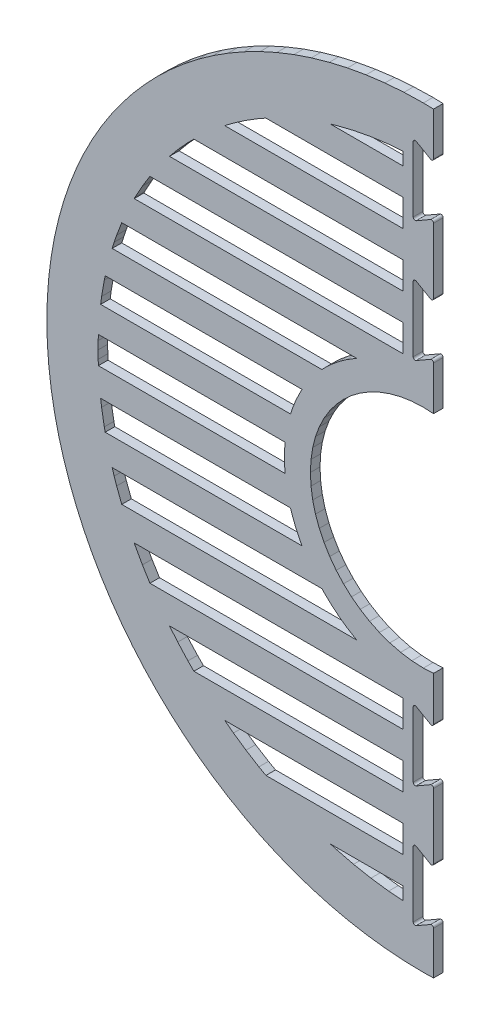
SolidWorks part; units mm, degrees
ref_plane "Front Plane" through (0, 0, 0) normal (0, 0, 1) x (1, 0, 0)
ref_plane "Top Plane" through (0, 0, 0) normal (0, 1, 0) x (1, 0, 0)
ref_plane "Right Plane" through (0, 0, 0) normal (1, 0, 0) x (0, 0, -1)
sketch "Model" plane through (0, 0, 0) normal (0, 0, 1) x (1, 0, 0)
  line L0 (-29.1025, -97.3667) -> (-27.1353, -97.9361)
  line L1 (-27.1353, -97.9361) -> (-21.8097, -99.2536)
  line L2 (-21.8097, -99.2536) -> (-16.3779, -100.2869)
  line L3 (-16.3779, -100.2869) -> (-10.848, -101.0278)
  line L4 (-10.848, -101.0278) -> (-5.2283, -101.4679)
  line L5 (-5.2283, -101.4679) -> (-4, -101.5146)
  line L6 (-4, -101.5146) -> (-4, -97.3667)
  line L7 (-4, -97.3667) -> (-29.1025, -97.3667)
  line L8 (4, -91.5563) -> (4, -100.5663)
  line L9 (4, -100.5663) -> (6.4923, -101.4734)
  line L10 (6.4923, -101.4734) -> (8.9399, -101.2903)
  line L11 (8.9399, -101.2903) -> (16.2223, -100.3929)
  line L12 (16.2223, -100.3929) -> (23.3353, -98.9929)
  line L13 (23.3353, -98.9929) -> (23.9888, -98.8316)
  line L14 (23.9888, -98.8316) -> (4, -91.5563)
  line L15 (-62.0452, -80.4333) -> (-59.3119, -82.4998)
  line L16 (-59.3119, -82.4998) -> (-55.4039, -85.1786)
  line L17 (-55.4039, -85.1786) -> (-51.3677, -87.677)
  line L18 (-51.3677, -87.677) -> (-49.1681, -88.9)
  line L19 (-49.1681, -88.9) -> (-4, -88.9)
  line L20 (-4, -88.9) -> (-4, -80.4333)
  line L21 (-4, -80.4333) -> (-62.0452, -80.4333)
  line L22 (4, -73.5362) -> (4, -82.5462)
  line L23 (4, -82.5462) -> (37.2469, -94.6471)
  line L24 (37.2469, -94.6471) -> (41.3341, -92.9428)
  line L25 (41.3341, -92.9428) -> (45.5839, -90.9334)
  line L26 (45.5839, -90.9334) -> (48.1117, -89.5915)
  line L27 (48.1117, -89.5915) -> (4, -73.5362)
  line L28 (-79.2988, -63.5) -> (-76.7248, -66.6048)
  line L29 (-76.7248, -66.6048) -> (-73.5451, -70.098)
  line L30 (-73.5451, -70.098) -> (-71.6792, -71.9667)
  line L31 (-71.6792, -71.9667) -> (-4, -71.9667)
  line L32 (-4, -71.9667) -> (-4, -63.5)
  line L33 (-4, -63.5) -> (-79.2988, -63.5)
  line L34 (4, -55.5161) -> (4, -64.5262)
  line L35 (4, -64.5262) -> (57.3994, -83.962)
  line L36 (57.3994, -83.962) -> (57.6454, -83.8007)
  line L37 (57.6454, -83.8007) -> (61.4183, -81.0733)
  line L38 (61.4183, -81.0733) -> (65.0584, -78.18)
  line L39 (65.0584, -78.18) -> (65.4148, -77.8693)
  line L40 (65.4148, -77.8693) -> (4, -55.5161)
  line L41 (-90.3108, -46.5667) -> (-90.0607, -47.0729)
  line L42 (-90.0607, -47.0729) -> (-87.7545, -51.2354)
  line L43 (-87.7545, -51.2354) -> (-85.4115, -55.0333)
  line L44 (-85.4115, -55.0333) -> (-4, -55.0333)
  line L45 (-4, -55.0333) -> (-4, -46.5667)
  line L46 (-4, -46.5667) -> (-90.3108, -46.5667)
  line L47 (13.9184, -41.106) -> (13.6646, -41.1963)
  line L48 (13.6646, -41.1963) -> (9.1415, -42.427)
  line L49 (9.1415, -42.427) -> (4.4365, -43.1676)
  line L50 (4.4365, -43.1676) -> (4, -43.2008)
  line L51 (4, -43.2008) -> (4, -46.5061)
  line L52 (4, -46.5061) -> (72.4083, -71.4047)
  line L53 (72.4083, -71.4047) -> (75.1264, -68.5601)
  line L54 (75.1264, -68.5601) -> (78.18, -65.0584)
  line L55 (78.18, -65.0584) -> (78.5271, -64.6217)
  line L56 (78.5271, -64.6217) -> (13.9184, -41.106)
  line L57 (-97.2071, -29.6333) -> (-96.5817, -31.625)
  line L58 (-96.5817, -31.625) -> (-95.8036, -33.9098)
  line L59 (-95.8036, -33.9098) -> (-94.207, -38.1)
  line L60 (-94.207, -38.1) -> (-20.7604, -38.1)
  line L61 (-20.7604, -38.1) -> (-21.4848, -37.7079)
  line L62 (-21.4848, -37.7079) -> (-23.9895, -36.1628)
  line L63 (-23.9895, -36.1628) -> (-26.3777, -34.4565)
  line L64 (-26.3777, -34.4565) -> (-28.6418, -32.5965)
  line L65 (-28.6418, -32.5965) -> (-30.7744, -30.5904)
  line L66 (-30.7744, -30.5904) -> (-31.6842, -29.6333)
  line L67 (-31.6842, -29.6333) -> (-97.2071, -29.6333)
  line L68 (31.7453, -29.5744) -> (30.6825, -30.6825)
  line L69 (30.6825, -30.6825) -> (28.0009, -33.1492)
  line L70 (28.0009, -33.1492) -> (25.1189, -35.3861)
  line L71 (25.1189, -35.3861) -> (24.3655, -35.8984)
  line L72 (24.3655, -35.8984) -> (83.8612, -57.5531)
  line L73 (83.8612, -57.5531) -> (86.3569, -53.745)
  line L74 (86.3569, -53.745) -> (88.4468, -50.2121)
  line L75 (88.4468, -50.2121) -> (31.7453, -29.5744)
  line L76 (40.7776, -14.8418) -> (40.5732, -15.4165)
  line L77 (40.5732, -15.4165) -> (39.1128, -18.8121)
  line L78 (39.1128, -18.8121) -> (37.3789, -22.0511)
  line L79 (37.3789, -22.0511) -> (37.0937, -22.511)
  line L80 (37.0937, -22.511) -> (92.3359, -42.6176)
  line L81 (92.3359, -42.6176) -> (92.9428, -41.3341)
  line L82 (92.9428, -41.3341) -> (94.7589, -36.9789)
  line L83 (94.7589, -36.9789) -> (95.5572, -34.78)
  line L84 (95.5572, -34.78) -> (40.7776, -14.8418)
  line L85 (-100.8122, -12.7) -> (-100.5006, -14.9994)
  line L86 (-100.5006, -14.9994) -> (-99.6609, -19.8552)
  line L87 (-99.6609, -19.8552) -> (-99.3846, -21.1667)
  line L88 (-99.3846, -21.1667) -> (-37.8853, -21.1667)
  line L89 (-37.8853, -21.1667) -> (-38.7638, -19.5198)
  line L90 (-38.7638, -19.5198) -> (-40.0074, -16.8291)
  line L91 (-40.0074, -16.8291) -> (-41.069, -14.0429)
  line L92 (-41.069, -14.0429) -> (-41.4935, -12.7)
  line L93 (-41.4935, -12.7) -> (-100.8122, -12.7)
  line L94 (85.2546, -4) -> (101.2046, -9.8053)
  line L95 (101.2046, -9.8053) -> (101.2903, -8.9399)
  line L96 (101.2903, -8.9399) -> (101.6001, -4)
  line L97 (101.6001, -4) -> (85.2546, -4)
  line L98 (43.2008, -4) -> (43.1676, -4.4365)
  line L99 (43.1676, -4.4365) -> (42.932, -6.3385)
  line L100 (42.932, -6.3385) -> (42.8879, -6.5999)
  line L101 (42.8879, -6.5999) -> (98.134, -26.7078)
  line L102 (98.134, -26.7078) -> (98.4177, -25.6655)
  line L103 (98.4177, -25.6655) -> (99.9812, -18.6131)
  line L104 (99.9812, -18.6131) -> (100.0206, -18.3844)
  line L105 (100.0206, -18.3844) -> (60.4997, -4)
  line L106 (60.4997, -4) -> (43.2008, -4)
  line L107 (-101.5066, 4.2333) -> (-101.5689, 2.5406)
  line L108 (-101.5689, 2.5406) -> (-101.6001, 0)
  line L109 (-101.6001, 0) -> (-101.5689, -2.5406)
  line L110 (-101.5689, -2.5406) -> (-101.5066, -4.2333)
  line L111 (-101.5066, -4.2333) -> (-43.1862, -4.2333)
  line L112 (-43.1862, -4.2333) -> (-43.1946, -4.1628)
  line L113 (-43.1946, -4.1628) -> (-43.342, -2.0942)
  line L114 (-43.342, -2.0942) -> (-43.3917, 0)
  line L115 (-43.3917, 0) -> (-43.342, 2.0942)
  line L116 (-43.342, 2.0942) -> (-43.1946, 4.1628)
  line L117 (-43.1946, 4.1628) -> (-43.1862, 4.2333)
  line L118 (-43.1862, 4.2333) -> (-101.5066, 4.2333)
  line L119 (101.2046, 9.8053) -> (85.2546, 4)
  line L120 (85.2546, 4) -> (101.6001, 4)
  line L121 (101.6001, 4) -> (101.2903, 8.9399)
  line L122 (101.2903, 8.9399) -> (101.2046, 9.8053)
  line L123 (-99.3846, 21.1667) -> (-99.6609, 19.8552)
  line L124 (-99.6609, 19.8552) -> (-100.5006, 14.9994)
  line L125 (-100.5006, 14.9994) -> (-100.8122, 12.7)
  line L126 (-100.8122, 12.7) -> (-41.4935, 12.7)
  line L127 (-41.4935, 12.7) -> (-41.069, 14.0429)
  line L128 (-41.069, 14.0429) -> (-40.0074, 16.8291)
  line L129 (-40.0074, 16.8291) -> (-38.7638, 19.5198)
  line L130 (-38.7638, 19.5198) -> (-37.8853, 21.1667)
  line L131 (-37.8853, 21.1667) -> (-99.3846, 21.1667)
  line L132 (98.134, 26.7078) -> (42.8879, 6.5999)
  line L133 (42.8879, 6.5999) -> (42.932, 6.3385)
  line L134 (42.932, 6.3385) -> (43.1676, 4.4366)
  line L135 (43.1676, 4.4366) -> (43.2008, 4)
  line L136 (43.2008, 4) -> (60.4997, 4)
  line L137 (60.4997, 4) -> (100.0206, 18.3844)
  line L138 (100.0206, 18.3844) -> (99.9812, 18.6131)
  line L139 (99.9812, 18.6131) -> (98.4177, 25.6655)
  line L140 (98.4177, 25.6655) -> (98.134, 26.7078)
  line L141 (0, 35.2778) -> (-3.607, 35.0956)
  line L142 (-3.607, 35.0956) -> (-7.1097, 34.5611)
  line L143 (-7.1097, 34.5611) -> (-10.4905, 33.6918)
  line L144 (-10.4905, 33.6918) -> (-13.7317, 32.5055)
  line L145 (-13.7317, 32.5055) -> (-16.8155, 31.0199)
  line L146 (-16.8155, 31.0199) -> (-19.7241, 29.2529)
  line L147 (-19.7241, 29.2529) -> (-22.4399, 27.2221)
  line L148 (-22.4399, 27.2221) -> (-24.9452, 24.9452)
  line L149 (-24.9452, 24.9452) -> (-27.2221, 22.4399)
  line L150 (-27.2221, 22.4399) -> (-29.2529, 19.7241)
  line L151 (-29.2529, 19.7241) -> (-31.0199, 16.8155)
  line L152 (-31.0199, 16.8155) -> (-32.5055, 13.7317)
  line L153 (-32.5055, 13.7317) -> (-33.6918, 10.4905)
  line L154 (-33.6918, 10.4905) -> (-34.5611, 7.1097)
  line L155 (-34.5611, 7.1097) -> (-35.0956, 3.607)
  line L156 (-35.0956, 3.607) -> (-35.2778, 0)
  line L157 (-35.2778, 0) -> (-35.0956, -3.607)
  line L158 (-35.0956, -3.607) -> (-34.5611, -7.1097)
  line L159 (-34.5611, -7.1097) -> (-33.6918, -10.4905)
  line L160 (-33.6918, -10.4905) -> (-32.5055, -13.7317)
  line L161 (-32.5055, -13.7317) -> (-31.0199, -16.8155)
  line L162 (-31.0199, -16.8155) -> (-29.2529, -19.7241)
  line L163 (-29.2529, -19.7241) -> (-27.2221, -22.4399)
  line L164 (-27.2221, -22.4399) -> (-24.9452, -24.9452)
  line L165 (-24.9452, -24.9452) -> (-22.4399, -27.222)
  line L166 (-22.4399, -27.222) -> (-19.7241, -29.2529)
  line L167 (-19.7241, -29.2529) -> (-16.8155, -31.0199)
  line L168 (-16.8155, -31.0199) -> (-13.7317, -32.5055)
  line L169 (-13.7317, -32.5055) -> (-10.4905, -33.6918)
  line L170 (-10.4905, -33.6918) -> (-7.1097, -34.5611)
  line L171 (-7.1097, -34.5611) -> (-3.607, -35.0956)
  line L172 (-3.607, -35.0956) -> (0, -35.2778)
  line L173 (0, -35.2778) -> (3.607, -35.0956)
  line L174 (3.607, -35.0956) -> (7.1097, -34.5611)
  line L175 (7.1097, -34.5611) -> (10.4905, -33.6918)
  line L176 (10.4905, -33.6918) -> (13.7317, -32.5055)
  line L177 (13.7317, -32.5055) -> (16.8155, -31.0199)
  line L178 (16.8155, -31.0199) -> (19.7241, -29.2529)
  line L179 (19.7241, -29.2529) -> (22.4399, -27.222)
  line L180 (22.4399, -27.222) -> (24.9452, -24.9452)
  line L181 (24.9452, -24.9452) -> (27.222, -22.4399)
  line L182 (27.222, -22.4399) -> (29.2529, -19.7241)
  line L183 (29.2529, -19.7241) -> (31.0199, -16.8155)
  line L184 (31.0199, -16.8155) -> (32.5055, -13.7317)
  line L185 (32.5055, -13.7317) -> (33.6918, -10.4905)
  line L186 (33.6918, -10.4905) -> (34.5611, -7.1097)
  line L187 (34.5611, -7.1097) -> (35.0956, -3.607)
  line L188 (35.0956, -3.607) -> (35.2778, 0)
  line L189 (35.2778, 0) -> (35.0956, 3.607)
  line L190 (35.0956, 3.607) -> (34.5611, 7.1097)
  line L191 (34.5611, 7.1097) -> (33.6918, 10.4905)
  line L192 (33.6918, 10.4905) -> (32.5055, 13.7317)
  line L193 (32.5055, 13.7317) -> (31.0199, 16.8155)
  line L194 (31.0199, 16.8155) -> (29.2529, 19.7241)
  line L195 (29.2529, 19.7241) -> (27.222, 22.4399)
  line L196 (27.222, 22.4399) -> (24.9452, 24.9452)
  line L197 (24.9452, 24.9452) -> (22.4399, 27.2221)
  line L198 (22.4399, 27.2221) -> (19.7241, 29.2529)
  line L199 (19.7241, 29.2529) -> (16.8155, 31.0199)
  line L200 (16.8155, 31.0199) -> (13.7317, 32.5055)
  line L201 (13.7317, 32.5055) -> (10.4905, 33.6918)
  line L202 (10.4905, 33.6918) -> (7.1097, 34.5611)
  line L203 (7.1097, 34.5611) -> (3.607, 35.0956)
  line L204 (3.607, 35.0956) -> (0, 35.2778)
  line L205 (-94.207, 38.1) -> (-95.8036, 33.9098)
  line L206 (-95.8036, 33.9098) -> (-96.5817, 31.625)
  line L207 (-96.5817, 31.625) -> (-97.2071, 29.6333)
  line L208 (-97.2071, 29.6333) -> (-31.6842, 29.6333)
  line L209 (-31.6842, 29.6333) -> (-30.7744, 30.5904)
  line L210 (-30.7744, 30.5904) -> (-28.6418, 32.5965)
  line L211 (-28.6418, 32.5965) -> (-26.3777, 34.4565)
  line L212 (-26.3777, 34.4565) -> (-23.9895, 36.1628)
  line L213 (-23.9895, 36.1628) -> (-21.4848, 37.7079)
  line L214 (-21.4848, 37.7079) -> (-20.7604, 38.1)
  line L215 (-20.7604, 38.1) -> (-94.207, 38.1)
  line L216 (92.3359, 42.6176) -> (37.0937, 22.511)
  line L217 (37.0937, 22.511) -> (37.3789, 22.0511)
  line L218 (37.3789, 22.0511) -> (39.1128, 18.8121)
  line L219 (39.1128, 18.8121) -> (40.5732, 15.4165)
  line L220 (40.5732, 15.4165) -> (40.7776, 14.8418)
  line L221 (40.7776, 14.8418) -> (95.5572, 34.78)
  line L222 (95.5572, 34.78) -> (94.7589, 36.9789)
  line L223 (94.7589, 36.9789) -> (92.9428, 41.3341)
  line L224 (92.9428, 41.3341) -> (92.3359, 42.6176)
  line L225 (-85.4115, 55.0333) -> (-87.7545, 51.2354)
  line L226 (-87.7545, 51.2354) -> (-90.0607, 47.0729)
  line L227 (-90.0607, 47.0729) -> (-90.3108, 46.5667)
  line L228 (-90.3108, 46.5667) -> (-4, 46.5667)
  line L229 (-4, 46.5667) -> (-4, 55.0333)
  line L230 (-4, 55.0333) -> (-85.4115, 55.0333)
  line L231 (83.8612, 57.5531) -> (24.3655, 35.8984)
  line L232 (24.3655, 35.8984) -> (25.1189, 35.3861)
  line L233 (25.1189, 35.3861) -> (28.0009, 33.1492)
  line L234 (28.0009, 33.1492) -> (30.6825, 30.6825)
  line L235 (30.6825, 30.6825) -> (31.7453, 29.5744)
  line L236 (31.7453, 29.5744) -> (88.4468, 50.2121)
  line L237 (88.4468, 50.2121) -> (86.3569, 53.745)
  line L238 (86.3569, 53.745) -> (83.8612, 57.5531)
  line L239 (72.4083, 71.4047) -> (4, 46.5061)
  line L240 (4, 46.5061) -> (4, 43.2008)
  line L241 (4, 43.2008) -> (4.4365, 43.1676)
  line L242 (4.4365, 43.1676) -> (9.1415, 42.427)
  line L243 (9.1415, 42.427) -> (13.6646, 41.1963)
  line L244 (13.6646, 41.1963) -> (13.9184, 41.106)
  line L245 (13.9184, 41.106) -> (78.5271, 64.6217)
  line L246 (78.5271, 64.6217) -> (78.18, 65.0584)
  line L247 (78.18, 65.0584) -> (75.1264, 68.5601)
  line L248 (75.1264, 68.5601) -> (72.4083, 71.4047)
  line L249 (-71.6792, 71.9667) -> (-73.5451, 70.098)
  line L250 (-73.5451, 70.098) -> (-76.7248, 66.6048)
  line L251 (-76.7248, 66.6048) -> (-79.2988, 63.5)
  line L252 (-79.2988, 63.5) -> (-4, 63.5)
  line L253 (-4, 63.5) -> (-4, 71.9667)
  line L254 (-4, 71.9667) -> (-71.6792, 71.9667)
  line L255 (57.3994, 83.9619) -> (4, 64.5262)
  line L256 (4, 64.5262) -> (4, 55.5161)
  line L257 (4, 55.5161) -> (65.4147, 77.8693)
  line L258 (65.4147, 77.8693) -> (65.0584, 78.18)
  line L259 (65.0584, 78.18) -> (61.4183, 81.0733)
  line L260 (61.4183, 81.0733) -> (57.6454, 83.8007)
  line L261 (57.6454, 83.8007) -> (57.3994, 83.9619)
  line L262 (-49.1681, 88.9) -> (-51.3677, 87.677)
  line L263 (-51.3677, 87.677) -> (-55.4039, 85.1786)
  line L264 (-55.4039, 85.1786) -> (-59.3119, 82.4998)
  line L265 (-59.3119, 82.4998) -> (-62.0452, 80.4333)
  line L266 (-62.0452, 80.4333) -> (-4, 80.4333)
  line L267 (-4, 80.4333) -> (-4, 88.9)
  line L268 (-4, 88.9) -> (-49.1681, 88.9)
  line L269 (37.2469, 94.6471) -> (4, 82.5462)
  line L270 (4, 82.5462) -> (4, 73.5362)
  line L271 (4, 73.5362) -> (48.1116, 89.5915)
  line L272 (48.1116, 89.5915) -> (45.5839, 90.9334)
  line L273 (45.5839, 90.9334) -> (41.3341, 92.9428)
  line L274 (41.3341, 92.9428) -> (37.2469, 94.6471)
  line L275 (6.4923, 101.4734) -> (4, 100.5663)
  line L276 (4, 100.5663) -> (4, 91.5563)
  line L277 (4, 91.5563) -> (23.9888, 98.8316)
  line L278 (23.9888, 98.8316) -> (23.3353, 98.9929)
  line L279 (23.3353, 98.9929) -> (16.2223, 100.3929)
  line L280 (16.2223, 100.3929) -> (8.9399, 101.2903)
  line L281 (8.9399, 101.2903) -> (6.4923, 101.4734)
  line L282 (-4, 101.5146) -> (-5.2283, 101.4679)
  line L283 (-5.2283, 101.4679) -> (-10.848, 101.0278)
  line L284 (-10.848, 101.0278) -> (-16.3779, 100.2869)
  line L285 (-16.3779, 100.2869) -> (-21.8097, 99.2536)
  line L286 (-21.8097, 99.2536) -> (-27.1353, 97.9361)
  line L287 (-27.1353, 97.9361) -> (-29.1025, 97.3667)
  line L288 (-29.1025, 97.3667) -> (-4, 97.3667)
  line L289 (-4, 97.3667) -> (-4, 101.5146)
  line L290 (0, 117.6001) -> (6.0517, 117.4471)
  line L291 (6.0517, 117.4471) -> (12.0239, 116.9929)
  line L292 (12.0239, 116.9929) -> (17.9093, 116.2451)
  line L293 (17.9093, 116.2451) -> (23.7005, 115.2109)
  line L294 (23.7005, 115.2109) -> (29.3901, 113.8977)
  line L295 (29.3901, 113.8977) -> (34.9707, 112.313)
  line L296 (34.9707, 112.313) -> (40.4348, 110.4642)
  line L297 (40.4348, 110.4642) -> (45.7753, 108.3585)
  line L298 (45.7753, 108.3585) -> (50.9845, 106.0035)
  line L299 (50.9845, 106.0035) -> (56.0552, 103.4064)
  line L300 (56.0552, 103.4064) -> (60.9799, 100.5747)
  line L301 (60.9799, 100.5747) -> (65.7513, 97.5159)
  line L302 (65.7513, 97.5159) -> (70.362, 94.2371)
  line L303 (70.362, 94.2371) -> (74.8046, 90.746)
  line L304 (74.8046, 90.746) -> (79.0716, 87.0497)
  line L305 (79.0716, 87.0497) -> (83.1558, 83.1558)
  line L306 (83.1558, 83.1558) -> (87.0497, 79.0717)
  line L307 (87.0497, 79.0717) -> (90.7459, 74.8046)
  line L308 (90.7459, 74.8046) -> (94.2371, 70.362)
  line L309 (94.2371, 70.362) -> (97.5158, 65.7513)
  line L310 (97.5158, 65.7513) -> (100.5747, 60.9799)
  line L311 (100.5747, 60.9799) -> (103.4064, 56.0552)
  line L312 (103.4064, 56.0552) -> (106.0035, 50.9845)
  line L313 (106.0035, 50.9845) -> (108.3585, 45.7753)
  line L314 (108.3585, 45.7753) -> (110.4642, 40.4349)
  line L315 (110.4642, 40.4349) -> (112.313, 34.9707)
  line L316 (112.313, 34.9707) -> (113.8977, 29.3901)
  line L317 (113.8977, 29.3901) -> (115.2109, 23.7005)
  line L318 (115.2109, 23.7005) -> (116.2451, 17.9093)
  line L319 (116.2451, 17.9093) -> (116.9929, 12.0239)
  line L320 (116.9929, 12.0239) -> (117.4471, 6.0517)
  line L321 (117.4471, 6.0517) -> (117.6001, 0)
  line L322 (117.6001, 0) -> (117.4471, -6.0517)
  line L323 (117.4471, -6.0517) -> (116.9929, -12.0239)
  line L324 (116.9929, -12.0239) -> (116.2451, -17.9093)
  line L325 (116.2451, -17.9093) -> (115.2109, -23.7005)
  line L326 (115.2109, -23.7005) -> (113.8977, -29.3901)
  line L327 (113.8977, -29.3901) -> (112.313, -34.9707)
  line L328 (112.313, -34.9707) -> (110.4642, -40.4348)
  line L329 (110.4642, -40.4348) -> (108.3585, -45.7753)
  line L330 (108.3585, -45.7753) -> (106.0035, -50.9845)
  line L331 (106.0035, -50.9845) -> (103.4064, -56.0552)
  line L332 (103.4064, -56.0552) -> (100.5747, -60.9799)
  line L333 (100.5747, -60.9799) -> (97.5158, -65.7513)
  line L334 (97.5158, -65.7513) -> (94.2371, -70.362)
  line L335 (94.2371, -70.362) -> (90.7459, -74.8046)
  line L336 (90.7459, -74.8046) -> (87.0497, -79.0716)
  line L337 (87.0497, -79.0716) -> (83.1558, -83.1558)
  line L338 (83.1558, -83.1558) -> (79.0716, -87.0497)
  line L339 (79.0716, -87.0497) -> (74.8046, -90.7459)
  line L340 (74.8046, -90.7459) -> (70.362, -94.2371)
  line L341 (70.362, -94.2371) -> (65.7513, -97.5158)
  line L342 (65.7513, -97.5158) -> (60.9799, -100.5747)
  line L343 (60.9799, -100.5747) -> (56.0552, -103.4064)
  line L344 (56.0552, -103.4064) -> (50.9845, -106.0035)
  line L345 (50.9845, -106.0035) -> (45.7753, -108.3585)
  line L346 (45.7753, -108.3585) -> (40.4348, -110.4642)
  line L347 (40.4348, -110.4642) -> (34.9707, -112.313)
  line L348 (34.9707, -112.313) -> (29.3901, -113.8977)
  line L349 (29.3901, -113.8977) -> (23.7005, -115.2109)
  line L350 (23.7005, -115.2109) -> (17.9093, -116.2451)
  line L351 (17.9093, -116.2451) -> (12.0239, -116.9929)
  line L352 (12.0239, -116.9929) -> (6.0517, -117.4471)
  line L353 (6.0517, -117.4471) -> (0, -117.6001)
  line L354 (0, -117.6001) -> (-6.0517, -117.4471)
  line L355 (-6.0517, -117.4471) -> (-12.0239, -116.9929)
  line L356 (-12.0239, -116.9929) -> (-17.9093, -116.2451)
  line L357 (-17.9093, -116.2451) -> (-23.7005, -115.2109)
  line L358 (-23.7005, -115.2109) -> (-29.3901, -113.8977)
  line L359 (-29.3901, -113.8977) -> (-34.9707, -112.313)
  line L360 (-34.9707, -112.313) -> (-40.4349, -110.4642)
  line L361 (-40.4349, -110.4642) -> (-45.7753, -108.3585)
  line L362 (-45.7753, -108.3585) -> (-50.9845, -106.0035)
  line L363 (-50.9845, -106.0035) -> (-56.0552, -103.4064)
  line L364 (-56.0552, -103.4064) -> (-60.9799, -100.5747)
  line L365 (-60.9799, -100.5747) -> (-65.7513, -97.5158)
  line L366 (-65.7513, -97.5158) -> (-70.362, -94.2371)
  line L367 (-70.362, -94.2371) -> (-74.8046, -90.7459)
  line L368 (-74.8046, -90.7459) -> (-79.0717, -87.0497)
  line L369 (-79.0717, -87.0497) -> (-83.1558, -83.1558)
  line L370 (-83.1558, -83.1558) -> (-87.0497, -79.0716)
  line L371 (-87.0497, -79.0716) -> (-90.746, -74.8046)
  line L372 (-90.746, -74.8046) -> (-94.2371, -70.362)
  line L373 (-94.2371, -70.362) -> (-97.5159, -65.7513)
  line L374 (-97.5159, -65.7513) -> (-100.5747, -60.9799)
  line L375 (-100.5747, -60.9799) -> (-103.4064, -56.0552)
  line L376 (-103.4064, -56.0552) -> (-106.0035, -50.9845)
  line L377 (-106.0035, -50.9845) -> (-108.3585, -45.7753)
  line L378 (-108.3585, -45.7753) -> (-110.4642, -40.4348)
  line L379 (-110.4642, -40.4348) -> (-112.313, -34.9707)
  line L380 (-112.313, -34.9707) -> (-113.8977, -29.3901)
  line L381 (-113.8977, -29.3901) -> (-115.2109, -23.7005)
  line L382 (-115.2109, -23.7005) -> (-116.2451, -17.9093)
  line L383 (-116.2451, -17.9093) -> (-116.9929, -12.0239)
  line L384 (-116.9929, -12.0239) -> (-117.4471, -6.0517)
  line L385 (-117.4471, -6.0517) -> (-117.6001, 0)
  line L386 (-117.6001, 0) -> (-117.4471, 6.0517)
  line L387 (-117.4471, 6.0517) -> (-116.9929, 12.0239)
  line L388 (-116.9929, 12.0239) -> (-116.2451, 17.9093)
  line L389 (-116.2451, 17.9093) -> (-115.2109, 23.7005)
  line L390 (-115.2109, 23.7005) -> (-113.8977, 29.3901)
  line L391 (-113.8977, 29.3901) -> (-112.313, 34.9707)
  line L392 (-112.313, 34.9707) -> (-110.4642, 40.4349)
  line L393 (-110.4642, 40.4349) -> (-108.3585, 45.7753)
  line L394 (-108.3585, 45.7753) -> (-106.0035, 50.9845)
  line L395 (-106.0035, 50.9845) -> (-103.4064, 56.0552)
  line L396 (-103.4064, 56.0552) -> (-100.5747, 60.9799)
  line L397 (-100.5747, 60.9799) -> (-97.5159, 65.7513)
  line L398 (-97.5159, 65.7513) -> (-94.2371, 70.362)
  line L399 (-94.2371, 70.362) -> (-90.746, 74.8046)
  line L400 (-90.746, 74.8046) -> (-87.0497, 79.0717)
  line L401 (-87.0497, 79.0717) -> (-83.1558, 83.1558)
  line L402 (-83.1558, 83.1558) -> (-79.0717, 87.0497)
  line L403 (-79.0717, 87.0497) -> (-74.8046, 90.746)
  line L404 (-74.8046, 90.746) -> (-70.362, 94.2371)
  line L405 (-70.362, 94.2371) -> (-65.7513, 97.5159)
  line L406 (-65.7513, 97.5159) -> (-60.9799, 100.5747)
  line L407 (-60.9799, 100.5747) -> (-56.0552, 103.4064)
  line L408 (-56.0552, 103.4064) -> (-50.9845, 106.0035)
  line L409 (-50.9845, 106.0035) -> (-45.7753, 108.3585)
  line L410 (-45.7753, 108.3585) -> (-40.4349, 110.4642)
  line L411 (-40.4349, 110.4642) -> (-34.9707, 112.313)
  line L412 (-34.9707, 112.313) -> (-29.3901, 113.8977)
  line L413 (-29.3901, 113.8977) -> (-23.7005, 115.2109)
  line L414 (-23.7005, 115.2109) -> (-17.9093, 116.2451)
  line L415 (-17.9093, 116.2451) -> (-12.0239, 116.9929)
  line L416 (-12.0239, 116.9929) -> (-6.0517, 117.4471)
  line L417 (-6.0517, 117.4471) -> (0, 117.6001)
extrude "Boss-Extrude1" add sketch "Model" along normal blind 3
sketch "Sketch1" plane through (0, 0, 3) normal (0, 0, 1) x (1, 0, 0)
  line L0 (-71.6562, 0) -> (-89.062, 0) construction
  line L1 (0, 55.4106) -> (0, 79.2155) construction
  line L2 (0, 200.1765) -> (0, 9.3221) construction
  line L6 (88.0963, 0) -> (149.8301, 0) construction
  line L7 (-6.35, -35.2778) -> (6.35, -35.2778)
  line L8 (-6.35, 113.995) -> (6.35, 113.995)
  line L9 (-6.35, 113.995) -> (-6.35, 35.2778)
  line L10 (-6.35, 35.2778) -> (6.35, 35.2778)
  line L11 (6.35, 113.995) -> (6.35, 35.2778)
  line L12 (-6.35, 113.995) -> (6.35, 35.2778) construction
  line L13 (-6.35, 35.2778) -> (6.35, 113.995) construction
  line L14 (6.35, -113.995) -> (6.35, -35.2778)
  line L15 (-6.35, -113.995) -> (-6.35, -35.2778)
  line L16 (-6.35, -113.995) -> (6.35, -113.995)
  line L17 (-76.6035, 4.2333) -> (-66.7089, -4.2333) construction
  line L18 (-43.1862, 4.2333) -> (-101.5066, 4.2333) construction
  line L19 (-101.5066, -4.2333) -> (-43.1862, -4.2333) construction
  line L20 (-4, 50.8) -> (4, 60.0211) construction
  line L21 (-4, 46.5667) -> (-4, 55.0333) construction
  line L22 (4, 64.5262) -> (4, 55.5161) construction
  point P15 (0, 0)
  point P16 (0, 74.6364)
  dimension "D1" = 12.7
extrude "Boss-Extrude2" add sketch "Sketch1" against normal up to surface (3 mm away) up to face at (12.4255, 99.0148, 0)
ref_plane "Plane1" through (0, 0, 0) normal (1, 0, 0) x (0, 0, -1)
ref_plane "Plane2" through (0, 0, 0) normal (0, -1, 0) x (-1, 0, 0)
ref_axis "Axis1" through (0, 0, 3.15) along (0, 0, -1)
sketch "Sketch4" plane through (0, 0, 3) normal (0, 0, 1) x (1, 0, 0)
  line L0 (0, 262.4993) -> (0, -109.6215) construction
  line L1 (0, -1.65) -> (0, 1.65) construction
  line L2 (-3.175, 106.6313) -> (-3.175, 84.0589)
  line L3 (3.175, 252.3742) -> (3.175, 102.9651)
  line L4 (-3.175, 106.6313) -> (3.175, 102.9651)
  line L5 (132.8797, 95.3451) -> (156.548, 95.3451) construction
  line L6 (-3.175, 84.0589) -> (3.175, 87.7251)
  line L7 (-3.175, 68.8189) -> (3.175, 65.1528)
  line L8 (-3.175, 46.2466) -> (3.175, 49.9128)
  line L9 (0, 116.1563) -> (163.0074, 116.1563) construction
  line L11 (3.175, 87.7251) -> (3.175, 65.1528)
  line L12 (-3.175, 68.8189) -> (-3.175, 46.2466)
  line L13 (3.175, 49.9128) -> (3.175, -49.9128)
  line L14 (-1.65, 0) -> (1.65, 0) construction
  line L15 (120.2007, 0) -> (342.421, 0) construction
  line L16 (-3.175, -68.8189) -> (-3.175, -46.2466)
  line L17 (3.175, -87.7251) -> (3.175, -65.1528)
  line L18 (-3.175, -46.2466) -> (3.175, -49.9128)
  line L19 (-3.175, -68.8189) -> (3.175, -65.1528)
  line L20 (-3.175, -84.0589) -> (3.175, -87.7251)
  line L21 (-3.175, -106.6313) -> (3.175, -102.9651)
  line L22 (3.175, -252.3742) -> (3.175, -102.9651)
  line L23 (-3.175, -106.6313) -> (-3.175, -84.0589)
  line L24 (3.175, 252.3742) -> (344.4313, 252.3742)
  line L25 (344.4313, 252.3742) -> (344.4313, -252.3742)
  line L26 (344.4313, -252.3742) -> (3.175, -252.3742)
  line L27 (0, 35.2778) -> (0, 117.6001) construction
  line L28 (0, 35.2778) -> (-3.607, 35.0956) construction
  line L29 (6.0517, 117.4471) -> (0, 117.6001) construction
  line L30 (3.175, 76.4389) -> (0, 76.4389) construction
  point P5 (3.175, 0)
  dimension "D1" = 3.175
  dimension "D2" = 60
  dimension "D3" = 7.62
  dimension "D4" = 2
  dimension "D5" = 9.525
  dimension "D6" = 6.35
  dimension "D7" = 22.5723
extrude "Cut-Extrude1" cut sketch "Sketch4" against normal through all both and the other way through all
fillet "Fillet1" radius 0.635 16 edges at (3.175, 102.9651, 1.5) (-3.175, -46.2466, 1.5) (-3.175, -84.0589, 1.5) (-3.175, -106.6313, 1.5) (3.175, -102.9651, 1.5) (3.175, -87.7251, 1.5) (3.175, -49.9128, 1.5) (-3.175, -68.8189, 1.5) (3.175, -65.1528, 1.5) (-3.175, 46.2466, 1.5) (3.175, 49.9128, 1.5) (-3.175, 106.6313, 1.5) (-3.175, 84.0589, 1.5) (3.175, 65.1528, 1.5) (3.175, 87.7251, 1.5) (-3.175, 68.8189, 1.5)
